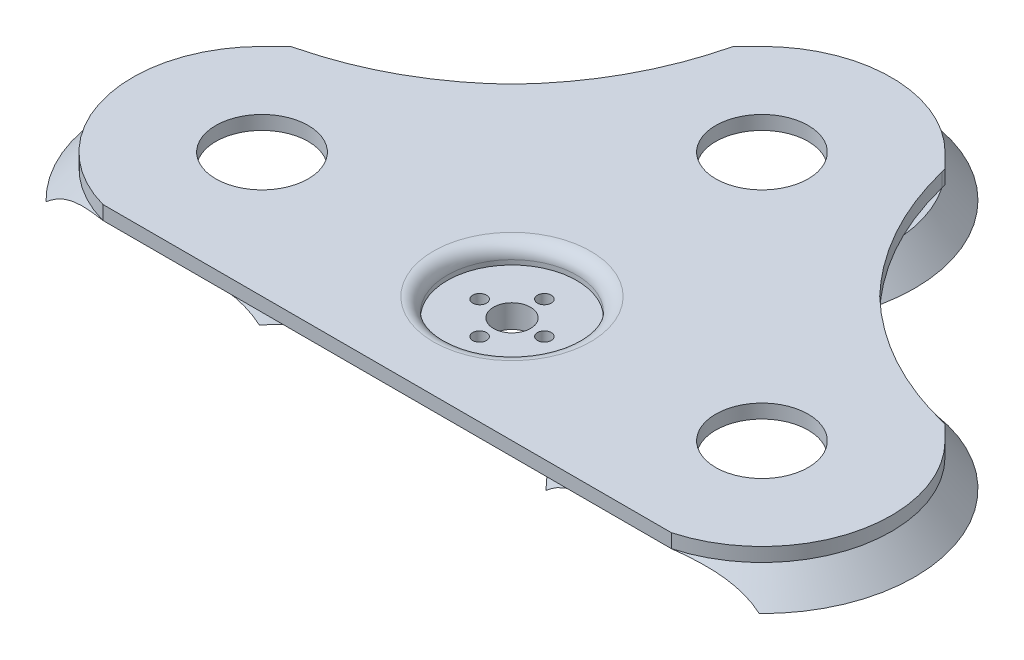
SolidWorks part; units mm, degrees
material "聚脂树脂"
ref_plane "前视基准面" through (0, 0, 0) normal (0, 0, 1) x (1, 0, 0)
ref_plane "上视基准面" through (0, 0, 0) normal (0, 1, 0) x (1, 0, 0)
ref_plane "右视基准面" through (0, 0, 0) normal (1, 0, 0) x (0, 0, -1)
other "Configuration Table"
sketch "草图1" plane through (0, 0, 0) normal (0, 1, 0) x (1, 0, 0)
  line L0 (0, 0) -> (29.5032, 0) construction
  line L1 (0, 0) -> (0, 22.1158) construction
  line L2 (0, 0) -> (19.7523, 19.7523) construction
  circle A0 centre (0, 0) radius 19
  circle A2 centre (0, 0) radius 10
  point P25 (0, 0)
  dimension "D1" = 38
  dimension "D2" = 20
  dimension "D5" = 45
extrude "凸台-拉伸1" add sketch "草图1" along normal blind 3
sketch "草图4" plane through (0, 3, 0) normal (0, 1, 0) x (1, 0, 0)
  line L0 (0, 0) -> (17.3084, 0) construction
  line L1 (0, 0) -> (0, 13.0367) construction
  circle A12 centre (0, 0) radius 14
  circle A13 centre (0, 7) radius 1.5
  circle A14 centre (7, 0) radius 1.5
  circle A15 centre (0, -7) radius 1.5
  circle A16 centre (-7, 0) radius 1.5
  circle A17 centre (0, 0) radius 4
  dimension "D2" = 28
  dimension "D3" = 3
  dimension "D4" = 3
  dimension "D5" = 7
  dimension "D6" = 7
  dimension "D7" = 8
extrude "凸台-拉伸2" add sketch "草图4" along normal blind 5
sketch "草图5" plane through (0, 3, 0) normal (0, 1, 0) x (1, 0, 0)
  circle A0 centre (0, 0) radius 14
  circle A1 centre (0, 0) radius 19
  dimension "D1" = 28
  dimension "D2" = 38
extrude "凸台-拉伸3" add sketch "草图5" along normal blind 9
sketch "草图6" plane through (0, 12, 0) normal (0, 1, 0) x (1, 0, 0)
  line L0 (0, 0) -> (0, 59.8344) construction
  line L1 (0, 0) -> (91.3225, 0) construction
  line L2 (-54.06, -28) -> (54.06, -28)
  line L3 (0, 54.06) -> (-19.799, 73.859) construction
  line L4 (-54.06, 0) -> (-73.859, 19.799) construction
  line L5 (-73.859, 19.799) -> (-19.799, 73.859)
  line L6 (73.859, 19.799) -> (19.799, 73.859)
  circle A0 centre (0, 54.06) radius 28
  circle A1 centre (54.06, 0) radius 28
  circle A2 centre (-54.06, 0) radius 28
  circle A3 centre (0, 0) radius 25
  circle M9 centre (0, 0) radius 19
  circle M10 centre (0, 0) radius 14
  dimension "D1" = 56
  dimension "D2" = 56
  dimension "D3" = 54.06
  dimension "D5" = 50
  dimension "D4" = 54.06
extrude "凸台-拉伸4" add sketch "草图6" against normal blind 3 contours A3 A2 | A3 A0 L5 A2 | A3 A0 | A3 A1 L6 A0 | A3 A1 | A1 A3 A0 M9 | A0 A3 M9 | A0 A3 A2 M9 | A2 A3 M9 | A2 A3 A1 M9 | A2 A1 A0 M9 M10 | A1 A3 M9 | A1 M9 | A0 M9 | A2 M9 | A3 A2 L2 A1 | A1 region at (-32.9922, 12, 21.0678) region at (-54.06, 12, 0) region at (54.06, 12, 0) region at (0, 12, -54.06) region at (-24.2929, 12, 0) region at (-18.4626, 12, 0)
sketch "草图8" plane through (0, 0, 0) normal (1, 0, 0) x (0, 0, -1)
  line L0 (54.06, 9) -> (54.06, -32.1282) construction
  line L2 (0, 0) -> (0, 36.8429) construction
  line L5 (82.06, 9) -> (80.06, 9)
  line L7 (80.06, 9) -> (85.0946, 3)
  line L8 (85.0946, 3) -> (87.0946, 3)
  line L9 (87.0946, 3) -> (82.06, 9)
  line L12 (73.859, 9) -> (82.06, 9) construction
  point P8 (54.06, 9)
  dimension "D1" = 54.06
  dimension "D2" = 2
  dimension "D3" = 6
  dimension "D4" = 26
  dimension "D5" = 130
revolve "旋转1" add sketch "草图8" angle 360 about L0
ref_axis "基准轴1" through (0, -0.6, 0) along (0, 1, 0)
pattern_circular "阵列(圆周)1" count 2 every 90 about axis through (0, -0.6, 0) along (0, 1, 0) of "旋转1"
pattern_circular "阵列(圆周)2" count 2 over 90 about axis through (0, -0.6, 0) along (0, 1, 0) of "旋转1" reverse direction yes
chamfer "倒角1" distance 3 angle 45 1 edges at (0, 0, 19)
sketch "草图9" plane through (0, 9, 0) normal (0, -1, 0) x (1, 0, 0)
  circle A0 centre (0, -54.06) radius 10
  circle A1 centre (-54.06, 0) radius 10
  circle A2 centre (54.06, 0) radius 10
  dimension "D1" = 20
  dimension "D2" = 20
  dimension "D3" = 20
extrude "切除-拉伸1" cut sketch "草图9" against normal blind 10
sketch "草图11" plane through (0, 9, 0) normal (0, -1, 0) x (1, 0, 0)
  line L0 (0, 0) -> (0, 50.3511) construction
  line L1 (0, 0) -> (89.0051, 0) construction
  line L3 (54.06, 0) -> (66.9541, 30.3767)
  line L4 (54.06, 0) -> (41.1659, 30.3767)
  line L5 (-54.06, 0) -> (-66.9541, 30.3767)
  line L6 (-54.06, 0) -> (-41.1659, 30.3767)
  arc A0 (41.1659, 30.3767) -> (66.9541, 30.3767) centre (54.06, 0) cw
  arc A2 (-41.1659, 30.3767) -> (-66.9541, 30.3767) centre (-54.06, 0) ccw
  dimension "D2" = 33
  dimension "D1" = 46
  dimension "D3" = 67
sketch "草图13" plane through (0, 9, 0) normal (0, -1, 0) x (1, 0, 0)
  line L0 (-75, 27) -> (75, 27)
  line L1 (0, 0) -> (98.71, 0) construction
  line L2 (-75, 27) -> (-75, 37)
  line L3 (-75, 37) -> (75, 37)
  line L4 (75, 37) -> (75, 27)
  line L5 (0, 0) -> (0, 50.3511) construction
  dimension "D1" = 27
  dimension "D2" = 150
  dimension "D3" = 10
  dimension "D4" = 75
extrude "切除-拉伸3" cut sketch "草图13" along normal blind 10 and the other way blind 10
sketch "草图14" plane through (0, 0, 0) normal (0, 0, 1) x (1, 0, 0)
  line L0 (0, 0) -> (84.8624, 0) construction
  line L1 (0, -0.6) -> (0, 12.6) construction
  line L2 (0, 0) -> (0, 21.5403) construction
  line L3 (54.06, 9) -> (54.06, 19.8553) construction
  line L4 (41.1659, 9) -> (66.9541, 9) construction
  line L5 (46.6438, 9) -> (61.4762, 9)
  line L6 (28, 0) -> (80.12, 0)
  line L7 (-46.6438, 9) -> (-61.4762, 9)
  line L8 (-28, 0) -> (-80.12, 0)
  spline S0 degree 2 poles (28, 0) (34.9431, 8.1641) (46.6438, 9) knots 0 0 0 1 1 1
  spline S1 degree 2 poles (80.12, 0) (73.1769, 8.1641) (61.4762, 9) knots 0 0 0 1 1 1
  spline S2 degree 2 poles (-28, 0) (-34.9431, 8.1641) (-46.6438, 9) knots 0 0 0 1 1 1
  spline S3 degree 2 poles (-80.12, 0) (-73.1769, 8.1641) (-61.4762, 9) knots 0 0 0 1 1 1
  dimension "D3" = 31
  dimension "D1" = 28
  dimension "D2" = 3
extrude "切除-拉伸5" cut sketch "草图14" along normal blind 37
fillet "圆角2" radius 1 3 edges at (54.06, 3, -31.0346) (0, 3, -23.0254) (-54.06, 3, -31.0346)
fillet "圆角3" radius 3 2 edges at (0, 9, 19) (0, 12, 14)
sketch "草图15" plane through (0, 12, 0) normal (0, 1, 0) x (1, 0, 0)
  line L0 (0, 0) -> (0, 95.1763) construction
  line L1 (-46.829, 46.829) -> (-15.0434, 15.0434) construction
  line L2 (-69.8156, 23.1465) -> (-70.7662, 22.8918)
  line L3 (-73.859, 19.799) -> (-19.799, 73.859) construction
  line L6 (73.859, 19.799) -> (19.799, 73.859) construction
  line L7 (70.7662, 22.8918) -> (22.8918, 70.7662)
  line L8 (-70.7662, 22.8918) -> (-22.8918, 70.7662)
  line L9 (-23.1465, 69.8156) -> (-22.8918, 70.7662)
  line L10 (23.1465, 69.8156) -> (22.8918, 70.7662)
  line L11 (69.8156, 23.1465) -> (70.7662, 22.8918)
  arc A0 (-73.859, 19.799) -> (-61.4762, -27) centre (-54.06, 0) ccw construction
  arc A1 (-73.859, 19.799) -> (-61.4762, -27) centre (-54.06, 0) ccw construction
  spline S0 degree 2 poles (-69.8156, 23.1465) (-52.5274, 27.5202) (-39.7579, 39.7579) knots 0 0 0 1 1 1
  spline S1 degree 2 poles (-23.1465, 69.8156) (-27.5202, 52.5274) (-39.7579, 39.7579) knots 0 0 0 1 1 1
  spline S2 degree 2 poles (23.1465, 69.8156) (27.5202, 52.5274) (39.7579, 39.7579) knots 0 0 0 1 1 1
  spline S3 degree 2 poles (69.8156, 23.1465) (52.5274, 27.5202) (39.7579, 39.7579) knots 0 0 0 1 1 1
  dimension "D1" = 8
  dimension "D2" = 10
  dimension "D3" = 15
  dimension "D4" = 33
  dimension "D5" = 30
extrude "切除-拉伸6" cut sketch "草图15" against normal blind 3
